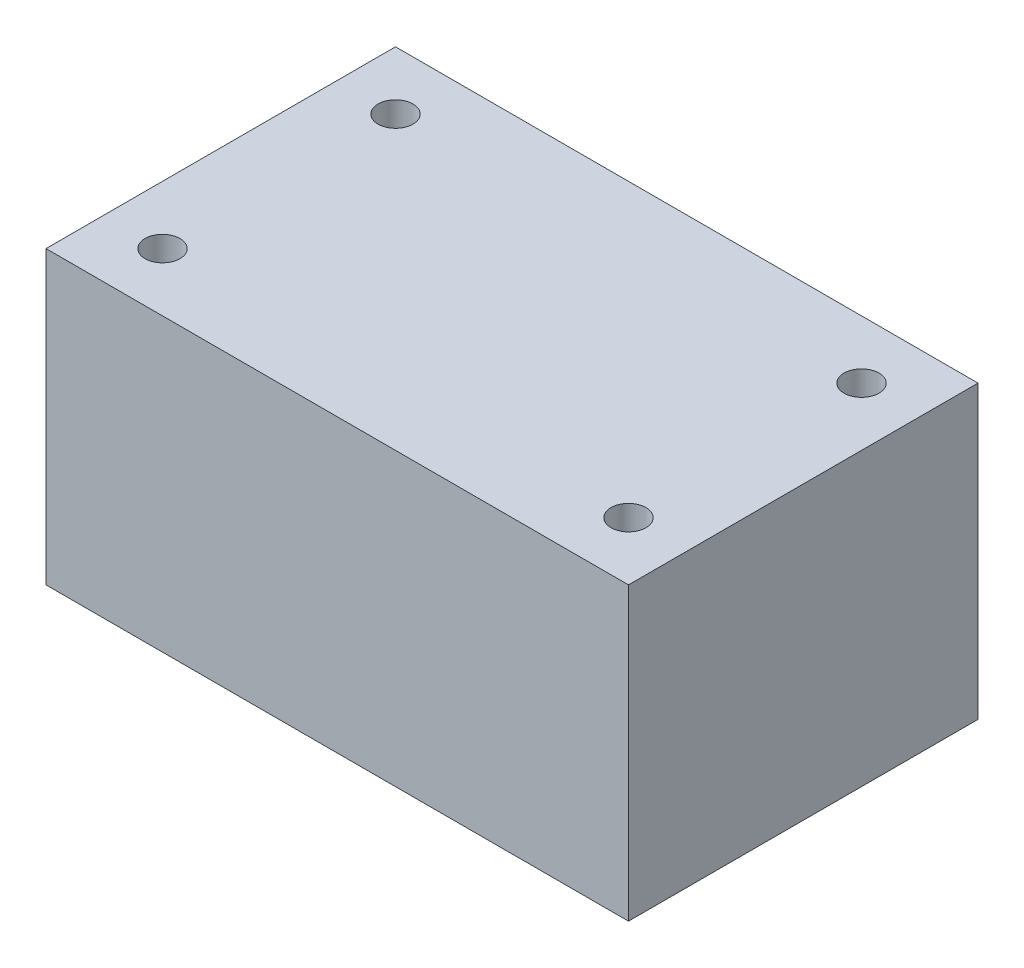
SolidWorks part; units mm, degrees
ref_plane "Plan de face" through (0, 0, 0) normal (0, 0, 1) x (1, 0, 0)
ref_plane "Plan de dessus" through (0, 0, 0) normal (0, 1, 0) x (1, 0, 0)
ref_plane "Plan de droite" through (0, 0, 0) normal (1, 0, 0) x (0, 0, -1)
sketch "Esquisse1" plane through (0, 0, 0) normal (0, 1, 0) x (1, 0, 0)
  line L0 (0, 15) -> (0, -15) construction
  line L1 (-25, -15) -> (25, -15)
  line L2 (-25, -15) -> (-25, 15)
  line L3 (-25, 15) -> (25, 15)
  line L4 (25, -15) -> (25, 15)
  line L5 (-25, -15) -> (25, 15) construction
  line L6 (-25, 15) -> (25, -15) construction
  line L8 (25, 0) -> (-25, 0) construction
  circle A0 centre (-20, 10) radius 1.5
  circle A1 centre (-20, -10) radius 1.5
  circle A2 centre (20, -10) radius 1.5
  circle A3 centre (20, 10) radius 1.5
  point P0 (0, 0)
  dimension "D3" = 3
  dimension "D4" = 10
  dimension "D1" = 30
  dimension "D2" = 50
  dimension "D5" = 20
extrude "Boss.-Extru.1" add sketch "Esquisse1" along normal blind 25
